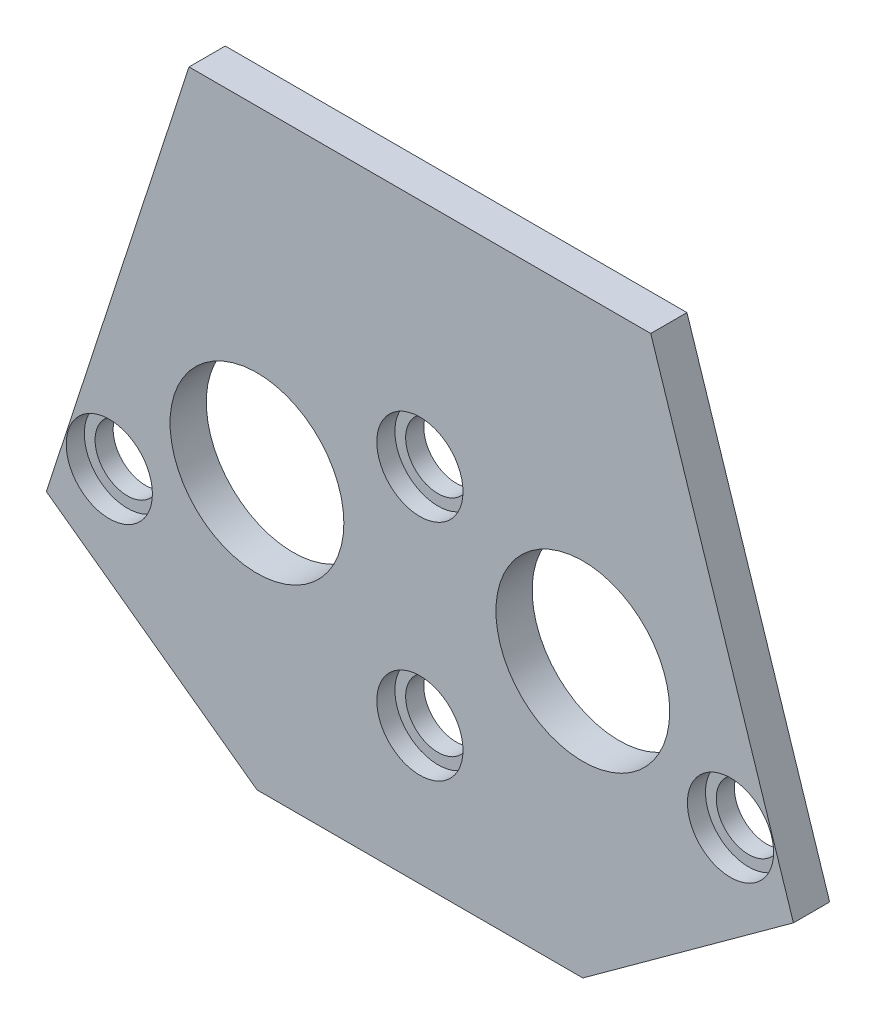
SolidWorks part; units mm, degrees
ref_plane "Front Plane" through (0, 0, 0) normal (0, 0, 1) x (1, 0, 0)
ref_plane "Top Plane" through (0, 0, 0) normal (0, 1, 0) x (1, 0, 0)
ref_plane "Right Plane" through (0, 0, 0) normal (1, 0, 0) x (0, 0, -1)
sketch "Sketch1" plane through (0, 0, 0) normal (0, 0, 1) x (1, 0, 0)
  line L1 (-304.8, 230.1875) -> (304.8, 230.1875)
  line L2 (-304.8, 230.1875) -> (-304.8, -230.1875)
  line L3 (-304.8, -230.1875) -> (304.8, -230.1875)
  line L4 (304.8, 230.1875) -> (304.8, -230.1875)
  line L5 (-304.8, 230.1875) -> (304.8, -230.1875) construction
  line L6 (-304.8, -230.1875) -> (304.8, 230.1875) construction
  point P0 (0, 0)
  dimension "D1" = 460.375
  dimension "D2" = 609.6
extrude "Boss-Extrude1" [suppressed] add sketch "Sketch1" along normal blind 5.334
sketch "Sketch2" plane through (0, 0, 0) normal (0, 0, 1) x (1, 0, 0)
  line L0 (-37.5261, 4.1449) -> (-10.4739, 36.2724) construction
  line L1 (-24, 20.2087) -> (24, 20.2087) construction
  line L2 (-24, 20.2087) -> (-24, -20.2087) construction
  line L3 (-24, -20.2087) -> (24, -20.2087)
  line L4 (24, 20.2087) -> (24, -20.2087) construction
  line L5 (-24, 20.2087) -> (24, -20.2087) construction
  line L6 (-24, -20.2087) -> (24, 20.2087) construction
  line L7 (0, -37.6457) -> (55.0228, 2.3307)
  line L8 (55.0228, 2.3307) -> (34.0059, 67.0138)
  line L9 (34.0059, 67.0138) -> (-34.0059, 67.0138)
  line L10 (-34.0059, 67.0138) -> (-55.0228, 2.3307)
  line L11 (-55.0228, 2.3307) -> (0, -37.6457)
  line L12 (-13.5261, -16.0637) -> (-47.1372, 12.2377) construction
  line L13 (13.5261, 16.0637) -> (-25.038, 48.5358) construction
  circle A0 centre (0, 0) radius 4.7625
  circle A1 centre (0, 0) radius 21 construction
  circle A2 centre (24, 20.2087) radius 12.8
  circle A3 centre (-24, 20.2087) radius 12.8
  circle A4 centre (0, 20.2087) radius 46.8052 construction
  point P0 (0, 0)
  point P21 (-24, 20.2087)
  dimension "D2" = 9.525
  dimension "D3" = 42
  dimension "D5" = 25.6
  dimension "D1" = 31.375
  dimension "D4" = 48
extrude "Boss-Extrude2" add sketch "Sketch2" along normal blind 5.334 contours L10 L11 L3 L7 L8 L9 A3 A2 A0 region at (0, 23.4369, 0)
sketch "Sketch3" plane through (0, 0, 5.334) normal (0, 0, 1) x (1, 0, 0)
  line L0 (55.0228, 2.3307) -> (36.4806, 17.367) construction
  line L1 (-55.0228, 2.3307) -> (-36.4806, 17.367) construction
  line L2 (-24, 33.0087) -> (24, 33.0087) construction
  circle A0 centre (0, 0) radius 6.35
  circle A1 centre (24, 20.2087) radius 12.8 construction
  circle A2 centre (-24, 20.2087) radius 12.8 construction
  circle A3 centre (45.7517, 9.8488) radius 6.35
  circle A4 centre (0, 33.0087) radius 6.35
  circle A5 centre (-45.7517, 9.8488) radius 6.35
  circle A6 centre (0, 0) radius 4.7625
  circle A7 centre (45.7517, 9.8488) radius 4.7625
  circle A8 centre (0, 33.0087) radius 4.7625
  circle A9 centre (-45.7517, 9.8488) radius 4.7625
  dimension "D1" = 12.7
extrude "Cut-Extrude3" cut sketch "Sketch3" against normal blind 2.667
extrude "Cut-Extrude4" cut sketch "Sketch3<2>" against normal through all contours A9 | A8 | A7 region at (45.7517, 9.8488, 5.334) region at (0, 33.0087, 5.334) region at (-45.7517, 9.8488, 5.334)
sketch "Sketch3<2>" plane through (0, 0, 5.334) normal (0, 0, 1) x (1, 0, 0) same geometry as "Sketch3"
